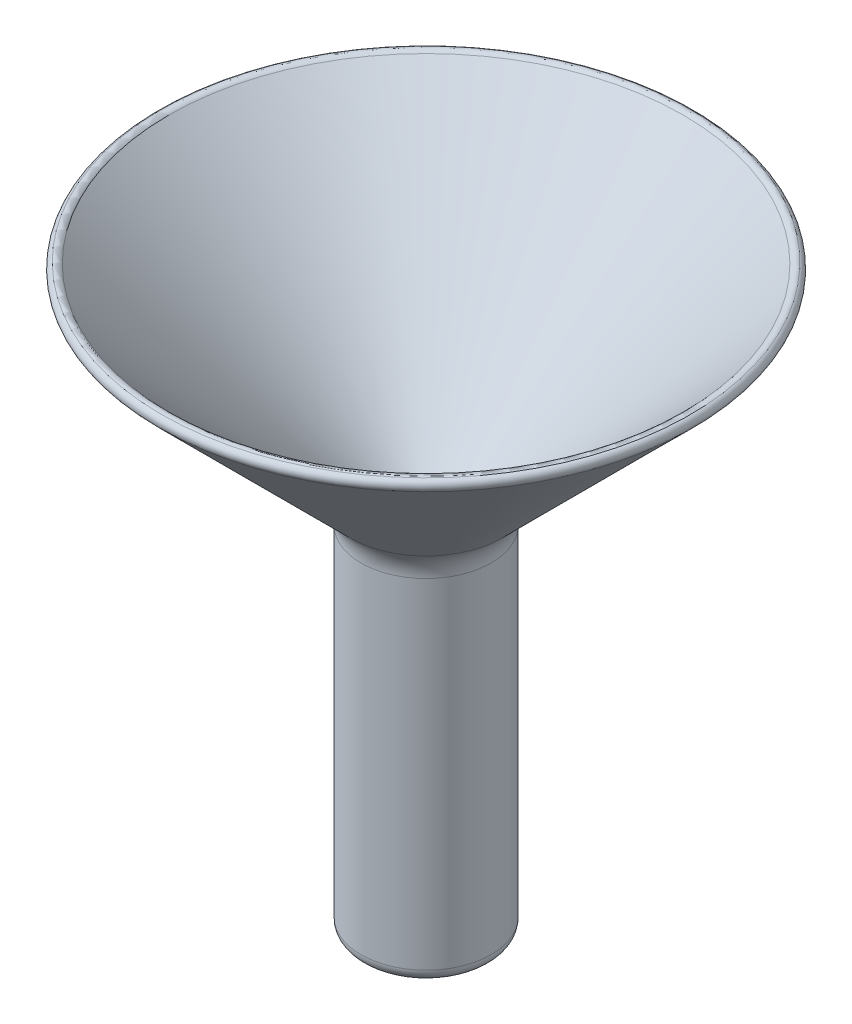
SolidWorks part; units mm, degrees
ref_plane "Спереди" through (0, 0, 0) normal (0, 0, 1) x (1, 0, 0)
ref_plane "Сверху" through (0, 0, 0) normal (0, 1, 0) x (1, 0, 0)
ref_plane "Справа" through (0, 0, 0) normal (1, 0, 0) x (0, 0, -1)
sketch "Эскиз2" plane through (0, 0, 0) normal (0, 0, 1) x (1, 0, 0)
  line L0 (0, 0) -> (3.8055, 0) construction
  line L1 (2.1, 0) -> (2.1, -5)
  line L2 (0, 0) -> (0, 2.8393) construction
  line L3 (2.6, -7.5) -> (2.6, -12)
  line L4 (3.7, 0) -> (3.7, -2.9149)
  line L5 (2.9, 0) -> (2.9, -3)
  line L6 (2.6, -12) -> (5, -12)
  line L7 (3.2502, -4.9875) -> (3.0498, -5.4273)
  line L8 (5, 0) -> (5, -12)
  line L9 (2.9, 0) -> (2.9, 5)
  line L10 (3.7, 5.8) -> (5.7, 5.8)
  line L11 (5.7, 5.8) -> (5.7, 10.8)
  line L12 (5.7, 10.8) -> (3.7, 10.8)
  line L14 (3.7, 0) -> (3.7, 5)
  line L15 (3.7, 5) -> (5, 5)
  line L16 (5, 5) -> (5, 0)
  line L17 (2.1, 14.8142) -> (2.1, 0)
  line L18 (3.1, 14.4) -> (3.1, 11.4)
  line L19 (3.7, 11.4) -> (3.7, 15)
  line L20 (3.7, 11.4) -> (5, 11.4)
  line L21 (5, 11.4) -> (5, 15.0574)
  line L24 (3.1, 14.4) -> (21, 32.3) construction
  line L25 (3.7, 15) -> (3.1, 14.4)
  line L26 (2.1, 14.8142) -> (20, 32.7142)
  line L27 (20, 32.7142) -> (20, 82.7142)
  line L30 (5.8787, 17.1787) -> (21, 32.3)
  line L31 (21, 32.3) -> (21, 82.7142)
  line L32 (20, 82.7142) -> (21, 82.7142)
  line L33 (3.1, 14.4) -> (3.1, 12.4235) construction
  line L34 (2.1, 14.8142) -> (2.1, 12.4235) construction
  line L35 (3.7, 5) -> (3.7, 11.4)
  line L36 (5, 11.4) -> (5, 5)
  line L37 (3.1, 11.4) -> (2.9, 5)
  line L38 (3.1, 14.4) -> (2.1, 14.4)
  line L39 (20, 32.7142) -> (21, 32.3)
  arc A0 (2.9, -3) -> (2.1, -5) centre (0, -3) cw
  arc A1 (2.6, -7.5) -> (3.0498, -5.4273) centre (7.6, -7.5) cw
  arc A2 (3.2502, -4.9875) -> (3.7, -2.9149) centre (-1.3, -2.9149) ccw
  arc A3 (2.9, 5) -> (3.7, 5.8) centre (3.7, 5) cw
  arc A4 (3.7, 10.8) -> (3.1, 11.4) centre (3.7, 11.4) cw
  arc A5 (5, 15.0574) -> (5.8787, 17.1787) centre (8, 15.0574) cw
  point P20 (3.7, -4)
  dimension "D4" = 5.2
  dimension "D8" = 5
  dimension "D12" = 5
  dimension "D14" = 5
  dimension "D17" = 0.6
  dimension "D18" = 3
  dimension "D1" = 4.2
  dimension "D2" = 5
  dimension "D3" = 5.8
  dimension "D5" = 2
  dimension "D6" = 0.8
  dimension "D7" = 12
  dimension "D9" = 4
  dimension "D10" = 4.5
  dimension "D11" = 10
  dimension "D13" = 5
  dimension "D15" = 2
  dimension "D16" = 135
  dimension "D19" = 40
  dimension "D20" = 50
  dimension "D21" = 1
  dimension "D22" = 3
revolve "Повернуть8" add sketch "Эскиз2" angle 360 about L2 region at (2.5317, 5.4657, 0) region at (10.1826, 21.6806, 0) region at (4.35, 11.1, 0) region at (4.35, 8.3, 0) region at (4.35, 5.4, 0) region at (4.0576, -4.7736, 0)
fillet "Скругление2" radius 1 1 edges at (0, -12, -5)
fillet "Скругление3" radius 1 1 edges at (0, 14.8142, -2.1)
fillet "Скругление4" radius 0.5 2 edges at (0, 32.7142, -20) (0, 32.3, -21)
